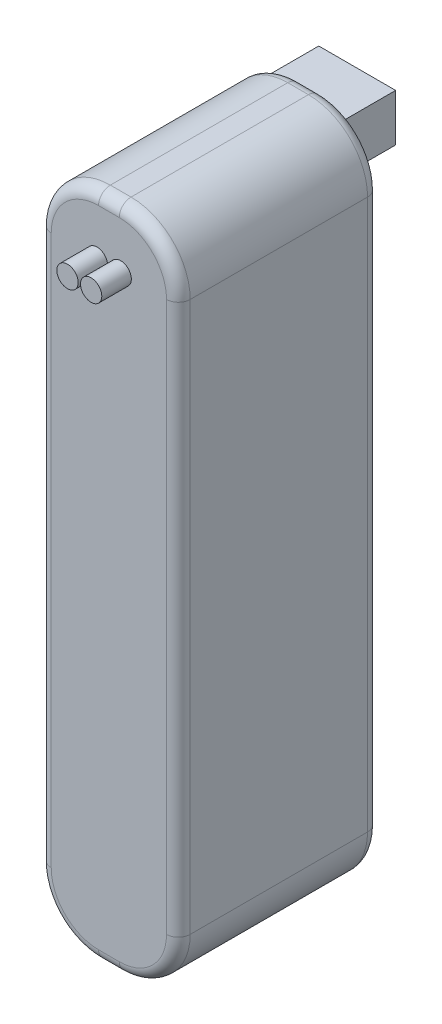
SolidWorks part; units mm, degrees
ref_plane "正面" through (0, 0, 0) normal (0, 0, 1) x (1, 0, 0)
ref_plane "平面" through (0, 0, 0) normal (0, 1, 0) x (1, 0, 0)
ref_plane "右側面" through (0, 0, 0) normal (1, 0, 0) x (0, 0, -1)
sketch "ｽｹｯﾁ1" plane through (0, 0, 0) normal (0, 1, 0) x (1, 0, 0)
  line L1 (-11.75, 17) -> (11.75, 17)
  line L2 (-11.75, 17) -> (-11.75, -17)
  line L3 (-11.75, -17) -> (11.75, -17)
  line L4 (11.75, 17) -> (11.75, -17)
  line L5 (-11.75, 17) -> (11.75, -17) construction
  line L6 (-11.75, -17) -> (11.75, 17) construction
  point P0 (0, 0)
  dimension "D1" = 34
  dimension "D2" = 23.5
extrude "ﾎﾞｽ - 押し出し1" add sketch "ｽｹｯﾁ1" along normal blind 113
sketch "ｽｹｯﾁ2" plane through (0, 0, 17) normal (0, 0, 1) x (1, 0, 0)
  line L0 (0, 0) -> (0, 113) construction
  line L1 (-11.75, 113) -> (11.75, 113) construction
  circle A0 centre (-2, 103) radius 1.8
  circle A1 centre (2, 103) radius 1.8
  dimension "D1" = 3.6
  dimension "D2" = 4
  dimension "D3" = 10
extrude "ﾎﾞｽ - 押し出し2" add sketch "ｽｹｯﾁ2" along normal blind 5
sketch "ｽｹｯﾁ3" plane through (0, 0, -17) normal (0, 0, -1) x (-1, 0, 0)
  line L0 (0, 113) -> (0, 107) construction
  line L1 (-11.75, 113) -> (11.75, 113) construction
  line L3 (-6.5, 103) -> (6.5, 103)
  line L4 (-6.5, 103) -> (-6.5, 111)
  line L5 (-6.5, 111) -> (6.5, 111)
  line L6 (6.5, 103) -> (6.5, 111)
  line L7 (-6.5, 103) -> (6.5, 111) construction
  line L8 (-6.5, 111) -> (6.5, 103) construction
  dimension "D1" = 13
  dimension "D2" = 8
  dimension "D3" = 2
extrude "ﾎﾞｽ - 押し出し3" add sketch "ｽｹｯﾁ3" along normal blind 8
fillet "ﾌｨﾚｯﾄ1" radius 10 4 edges at (11.75, 0, 0) (-11.75, 0, 0) (-11.75, 113, 0) (11.75, 113, 0)
fillet "ﾌｨﾚｯﾄ2" radius 2 16 edges at (8.8211, 110.0711, -17) (0, 113, -17) (-8.8211, 110.0711, -17) (-11.75, 56.5, -17) (-8.8211, 2.9289, -17) (0, 0, -17) (8.8211, 2.9289, -17) (8.8211, 110.0711, 17) (0, 113, 17) (-8.8211, 110.0711, 17) (-11.75, 56.5, 17) (-8.8211, 2.9289, 17) (0, 0, 17) (8.8211, 2.9289, 17) (11.75, 56.5, -17) (11.75, 56.5, 17)
